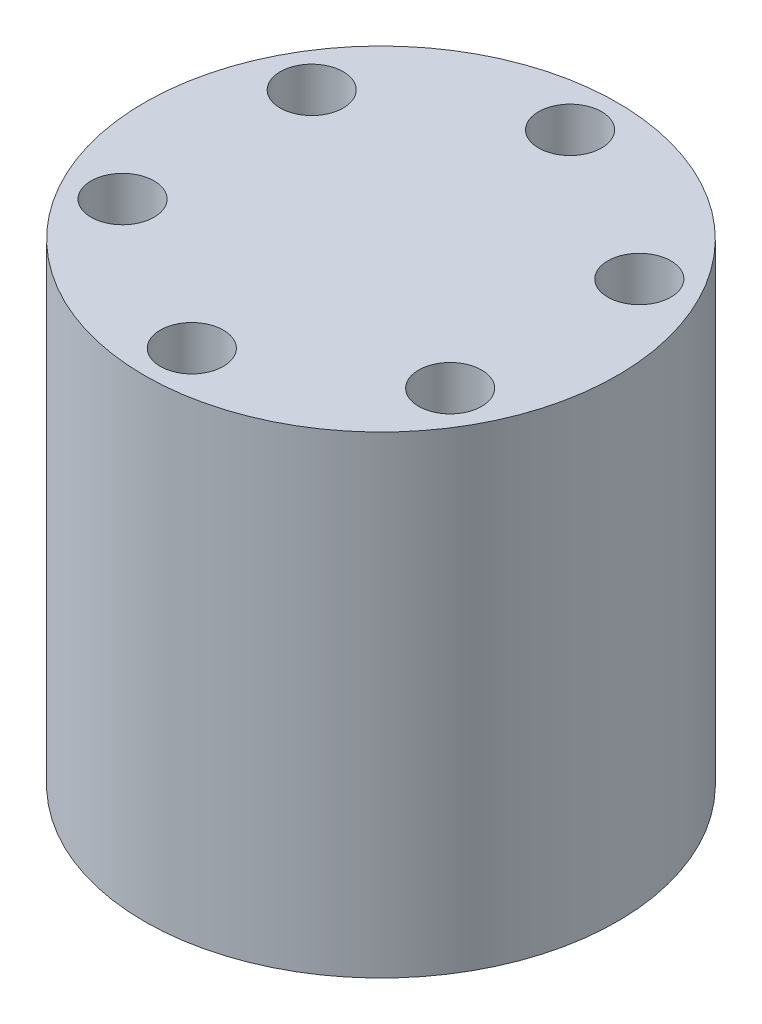
SolidWorks part; units mm, degrees
note: '?' marks a value the reader was unsure of.
material "1060 Alloy"
ref_plane "Front Plane" through (0, 0, 0) normal (0, 0, 1) x (1, 0, 0)
ref_plane "Top Plane" through (0, 0, 0) normal (0, 1, 0) x (1, 0, 0)
ref_plane "Right Plane" through (0, 0, 0) normal (1, 0, 0) x (0, 0, -1)
sketch "Sketch1" plane through (0, 0, 0) normal (0, 1, 0) x (1, 0, 0)
  circle A0 centre (0, 0) radius 15
extrude "Boss-Extrude1" add sketch "Sketch1" along normal blind 30
sketch "Sketch2" plane through (0, 0, 0) normal (0, -1, 0) x (1, 0, 0)
  circle A0 centre (0, 0) radius 7
extrude "Boss-Extrude2" add sketch "Sketch2" along normal blind 4
hole_wizard "Ø4.0mm Dowel Hole1" positions "Sketch3" profile "Sketch5" hole size "Ø4.0" standard "ISO" end condition through all
sketch "Sketch3" plane through (0, 0, 0) normal (0, -1, 0) x (-1, 0, 0)
  line L0 (0, 44.7868) -> (0, -44.7868) construction
  point P0 (0, -12)
  dimension "D1" = 12
sketch "Sketch5" plane through (0, 0, 12) normal (1, 0, 0) x (0, 0, -1)
  line L0 (0, 0) -> (0, 30)
  line L1 (0, 30) -> (2, 30)
  line L2 (2, 30) -> (2, 0)
  line L5 (2, 0) -> (0, 0)
  line L11 (0, -6.35) -> (0, 107.95) construction
  dimension "Thru Hole Dia." = 4
  dimension "Thru Hole Depth" = 30
pattern_circular "CirPattern1" count 6 over 360 about axis through (0, 0, 0) along (0, 1, 0) of "Ø4.0mm Dowel Hole1"
ref_axis "Axis1" through (0, 49.499, 0) along (0, -1, 0)?
